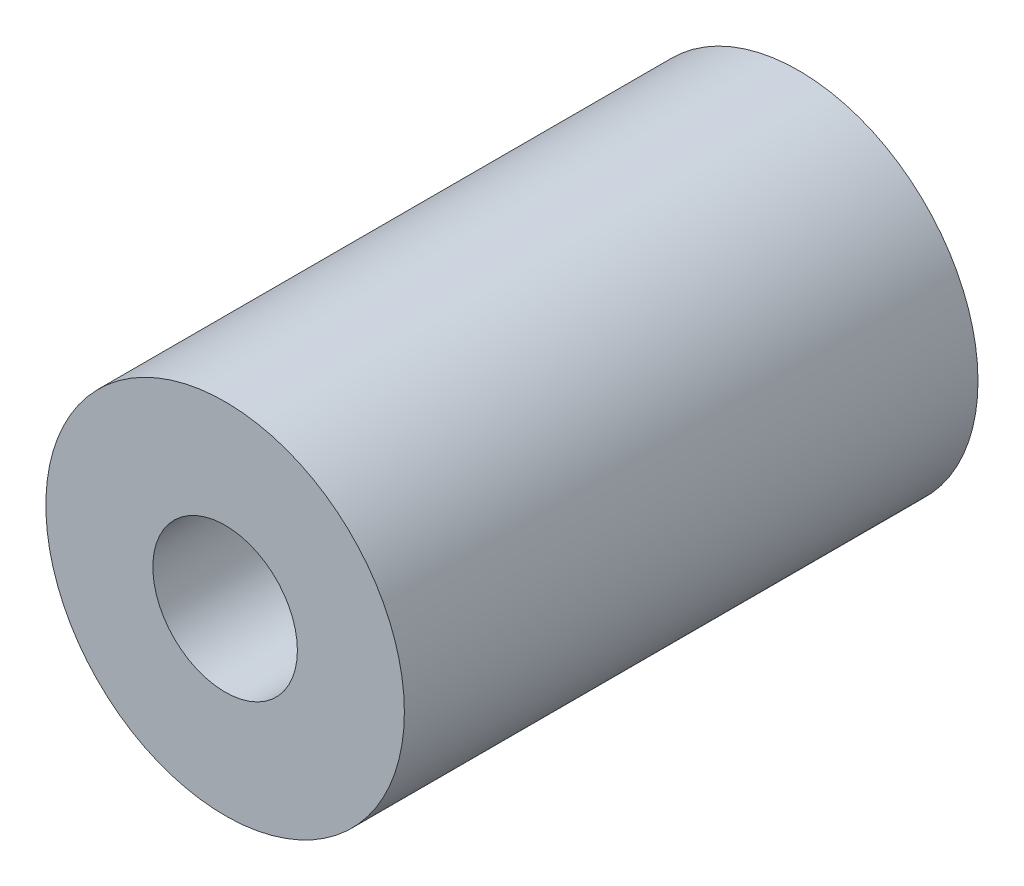
SolidWorks part; units mm, degrees
ref_plane "Front Plane" through (0, 0, 0) normal (0, 0, 1) x (1, 0, 0)
ref_plane "Top Plane" through (0, 0, 0) normal (0, 1, 0) x (1, 0, 0)
ref_plane "Right Plane" through (0, 0, 0) normal (1, 0, 0) x (0, 0, -1)
sketch "Sketch1" plane through (0, 0, 0) normal (0, 0, 1) x (1, 0, 0)
  circle A0 centre (0, 0) radius 7.9375
  circle A1 centre (0, 0) radius 3.2004
  dimension "OD" = 15.875
  dimension "ID" = 6.4008
extrude "Extrude1" add sketch "Sketch1" along normal mid plane 25.4
sketch "Sketch2" plane through (0, 0, 0) normal (1, 0, 0) x (0, 0, -1)
  line L0 (-12.7, -3.2004) -> (12.7, -3.2004) construction
  line L3 (12.7, 3.2004) -> (-12.7, 3.2004) construction
  line L5 (-12.7, -3.2004) -> (12.7, -3.2004)
  line L6 (12.7, 3.2004) -> (-12.7, 3.2004)
sketch "Sketch4" plane through (0, 0, 12.7) normal (0, 0, 1) x (1, 0, 0)
  line L0 (0, 0) -> (-2.263, 2.263)
  line L1 (0, -2.1828) -> (0, 2.1828) construction
  circle A0 centre (0, 0) radius 3.2004 construction
  dimension "D1" = 45
